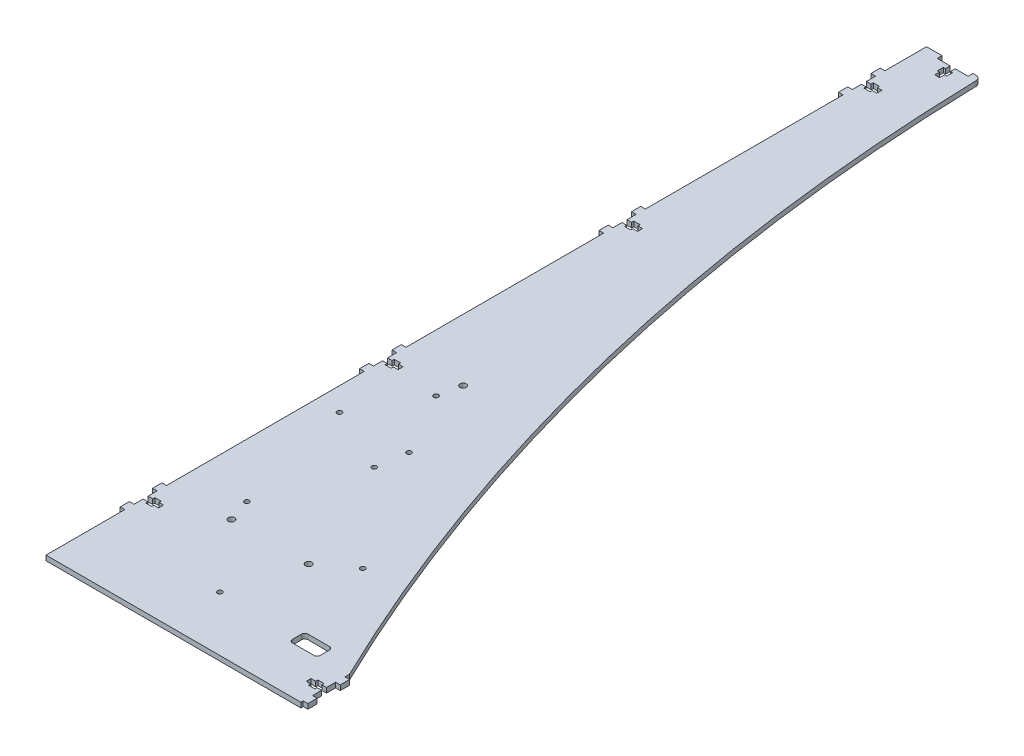
SolidWorks part; units mm, degrees
ref_plane "Alzado" through (0, 0, 0) normal (0, 0, 1) x (1, 0, 0)
ref_plane "Planta" through (0, 0, 0) normal (0, 1, 0) x (1, 0, 0)
ref_plane "Vista lateral" through (0, 0, 0) normal (1, 0, 0) x (0, 0, -1)
sketch "Croquis1" plane through (0, 0, 0) normal (0, 1, 0) x (1, 0, 0)
  line L0 (7, 66.1) -> (10, 66.1)
  line L1 (0, 0) -> (165, 0)
  line L2 (0, 0) -> (0, 51)
  line L3 (0, 570) -> (10, 570)
  line L4 (165, 0) -> (165, 1.5)
  line L5 (0, 51) -> (-3, 51)
  line L7 (0, 57) -> (-3, 57)
  line L8 (-3, 51) -> (-3, 57)
  line L9 (0, 72) -> (-3, 72)
  line L11 (0, 78) -> (-3, 78)
  line L12 (-3, 72) -> (-3, 78)
  line L13 (0, 66.1) -> (3, 66.1)
  line L15 (0, 62.9) -> (3, 62.9)
  line L16 (10, 66.1) -> (10, 62.9)
  line L17 (7, 67.5) -> (3, 67.5)
  line L18 (7, 67.5) -> (7, 66.1)
  line L19 (7, 61.5) -> (3, 61.5)
  line L20 (3, 67.5) -> (3, 66.1)
  line L21 (3, 62.9) -> (3, 61.5)
  line L22 (7, 62.9) -> (7, 61.5)
  line L23 (7, 62.9) -> (10, 62.9)
  line L24 (0, 66.1) -> (0, 72)
  line L25 (0, 78) -> (0, 206)
  line L26 (0, 57) -> (0, 62.9)
  line L27 (0, 233) -> (-3, 233)
  line L28 (-3, 227) -> (-3, 233)
  line L29 (0, 227) -> (-3, 227)
  line L30 (0, 221.1) -> (3, 221.1)
  line L31 (3, 222.5) -> (3, 221.1)
  line L32 (7, 222.5) -> (3, 222.5)
  line L33 (7, 222.5) -> (7, 221.1)
  line L34 (7, 221.1) -> (10, 221.1)
  line L35 (10, 221.1) -> (10, 217.9)
  line L36 (7, 217.9) -> (10, 217.9)
  line L37 (7, 217.9) -> (7, 216.5)
  line L38 (7, 216.5) -> (3, 216.5)
  line L39 (3, 217.9) -> (3, 216.5)
  line L40 (0, 217.9) -> (3, 217.9)
  line L41 (0, 212) -> (-3, 212)
  line L42 (-3, 206) -> (-3, 212)
  line L43 (0, 206) -> (-3, 206)
  line L44 (0, 388) -> (-3, 388)
  line L45 (-3, 382) -> (-3, 388)
  line L46 (0, 382) -> (-3, 382)
  line L47 (0, 376.1) -> (3, 376.1)
  line L48 (3, 377.5) -> (3, 376.1)
  line L49 (7, 377.5) -> (3, 377.5)
  line L50 (7, 377.5) -> (7, 376.1)
  line L51 (7, 376.1) -> (10, 376.1)
  line L52 (10, 376.1) -> (10, 372.9)
  line L53 (7, 372.9) -> (10, 372.9)
  line L54 (7, 372.9) -> (7, 371.5)
  line L55 (7, 371.5) -> (3, 371.5)
  line L56 (3, 372.9) -> (3, 371.5)
  line L57 (0, 372.9) -> (3, 372.9)
  line L58 (0, 367) -> (-3, 367)
  line L59 (-3, 361) -> (-3, 367)
  line L60 (0, 361) -> (-3, 361)
  line L61 (0, 388) -> (0, 516)
  line L62 (0, 376.1) -> (0, 382)
  line L63 (0, 367) -> (0, 372.9)
  line L64 (0, 233) -> (0, 361)
  line L65 (0, 221.1) -> (0, 227)
  line L66 (0, 212) -> (0, 217.9)
  line L67 (21.6, 566.9) -> (30, 566.9)
  line L69 (10, 570) -> (10, 566.9)
  line L70 (10, 566.9) -> (18.4, 566.9)
  line L71 (30, 570) -> (30, 566.9)
  line L73 (18.4, 566.9) -> (18.4, 563.9)
  line L74 (18.4, 556.9) -> (21.6, 556.9)
  line L75 (21.6, 566.9) -> (21.6, 563.9)
  line L76 (17, 563.9) -> (18.4, 563.9)
  line L77 (17, 563.9) -> (17, 559.9)
  line L78 (17, 559.9) -> (18.4, 559.9)
  line L79 (23, 563.9) -> (23, 559.9)
  line L80 (21.6, 563.9) -> (23, 563.9)
  line L81 (18.4, 559.9) -> (18.4, 556.9)
  line L82 (21.6, 559.9) -> (21.6, 556.9)
  line L83 (21.6, 559.9) -> (23, 559.9)
  line L84 (30, 570) -> (165, 570)
  line L85 (158, 13.4) -> (158, 12)
  line L86 (165, 1.5) -> (168, 1.5)
  line L88 (165, 7.5) -> (168, 7.5)
  line L89 (168, 1.5) -> (168, 7.5)
  line L90 (165, 22.5) -> (168, 22.5)
  line L92 (165, 28.5) -> (168, 28.5)
  line L93 (168, 22.5) -> (168, 28.5)
  line L94 (165, 16.6) -> (162, 16.6)
  line L96 (165, 13.4) -> (162, 13.4)
  line L97 (155, 16.6) -> (155, 13.4)
  line L98 (158, 18) -> (162, 18)
  line L99 (158, 18) -> (158, 16.6)
  line L100 (158, 12) -> (162, 12)
  line L101 (162, 18) -> (162, 16.6)
  line L102 (158, 16.6) -> (155, 16.6)
  line L103 (162, 13.4) -> (162, 12)
  line L104 (158, 13.4) -> (155, 13.4)
  line L105 (165, 16.6) -> (165, 22.5)
  line L106 (165, 7.5) -> (165, 13.4)
  line L107 (165, 28.5) -> (165, 570)
  line L108 (0, 543) -> (-3, 543)
  line L109 (-3, 537) -> (-3, 543)
  line L110 (0, 537) -> (-3, 537)
  line L111 (0, 531.1) -> (3, 531.1)
  line L112 (3, 532.5) -> (3, 531.1)
  line L113 (7, 532.5) -> (3, 532.5)
  line L114 (7, 532.5) -> (7, 531.1)
  line L115 (7, 531.1) -> (10, 531.1)
  line L116 (10, 531.1) -> (10, 527.9)
  line L117 (7, 527.9) -> (10, 527.9)
  line L118 (7, 527.9) -> (7, 526.5)
  line L119 (7, 526.5) -> (3, 526.5)
  line L120 (3, 527.9) -> (3, 526.5)
  line L121 (0, 527.9) -> (3, 527.9)
  line L122 (0, 522) -> (-3, 522)
  line L123 (-3, 516) -> (-3, 522)
  line L124 (0, 516) -> (-3, 516)
  line L125 (0, 543) -> (0, 570)
  line L126 (0, 522) -> (0, 527.9)
  line L127 (0, 531.1) -> (0, 537)
  dimension "D1" = 570
  dimension "D2" = 165
  dimension "D3" = 3
  dimension "D4" = 6
  dimension "D5" = 3
  dimension "D6" = 6
  dimension "D7" = 15
  dimension "D8" = 10
  dimension "D9" = 3.2
  dimension "D10" = 5.9
  dimension "D11" = 4
  dimension "D12" = 6
  dimension "D13" = 1.4
  dimension "D14" = 51
  dimension "D15" = 3
  dimension "D17" = 155
  dimension "D18" = 20
  dimension "D19" = 10
  dimension "D20" = 3.1
  dimension "D21" = 10
  dimension "D22" = 3.2
  dimension "D23" = 4
  dimension "D24" = 6
  dimension "D25" = 1.4
  dimension "D26" = 8.4
  dimension "D27" = 3
  dimension "D28" = 6
  dimension "D29" = 6
  dimension "D30" = 3
  dimension "D31" = 3
  dimension "D32" = 3.2
  dimension "D33" = 4
  dimension "D34" = 6
  dimension "D35" = 1.4
  dimension "D36" = 10
  dimension "D37" = 3
  dimension "D38" = 15
  dimension "D39" = 5.9
  dimension "D40" = 1.5
  dimension "D16" = 4
extrude "Saliente-Extruir1" add sketch "Croquis1" along normal blind 3.2
sketch "Croquis3" plane through (0, 3.2, 0) normal (0, 1, 0) x (1, 0, 0)
  line L0 (0, 217.9) -> (0, 212) construction
  line L1 (0, 0) -> (165, 0) construction
  circle A0 centre (40, 80) radius 2.05
  circle A1 centre (90, 80) radius 2.05
  circle A2 centre (40, 230) radius 2.05
  dimension "D1" = 4.1
  dimension "D2" = 50
  dimension "D3" = 150
  dimension "D4" = 40
  dimension "D5" = 80
extrude "Cortar-Extruir2" cut sketch "Croquis3" against normal up to surface (3.2 mm away) up to face at (34.1167, 0, -285.1383)
sketch "Croquis4" plane through (0, 0, 0) normal (0, -1, 0) x (1, 0, 0)
  line L1 (0, 0) -> (165, 0) construction
  line L4 (143, -30.5) -> (129, -30.5)
  line L5 (145, -32.5) -> (145, -38.5)
  line L6 (143, -40.5) -> (129, -40.5)
  line L7 (127, -32.5) -> (127, -38.5)
  line L8 (165, -28.5) -> (165, -570) construction
  arc A14 (143, -30.5) -> (145, -32.5) centre (143, -32.5) cw
  arc A15 (127, -38.5) -> (129, -40.5) centre (129, -38.5) ccw
  arc A16 (127, -32.5) -> (129, -30.5) centre (129, -32.5) cw
  arc A17 (145, -38.5) -> (143, -40.5) centre (143, -38.5) cw
  point P38 (145, -30.5)
  point P41 (127, -40.5)
  point P46 (145, -40.5)
  dimension "D3" = 20
  dimension "D20" = 2
  dimension "D16" = 18
  dimension "D17" = 10
  dimension "D19" = 30.5
extrude "Cortar-Extruir3" cut sketch "Croquis4" against normal up to surface (3.2 mm away) up to face at (40, 3.2, -227.95)
sketch "Croquis5" plane through (0, 0, 0) normal (0, -1, 0) x (1, 0, 0)
  line L0 (165, -570) -> (30, -570) construction
  line L1 (165, -28.5) -> (165, -570) construction
  line L2 (35, -570) -> (165, -570)
  line L3 (165, -570) -> (165, -31.5)
  arc A0 (35, -570) -> (165, -31.5) centre (1334.6806, -598.8159) cw
  dimension "D3" = 1300
  dimension "D1" = 5
  dimension "D2" = 3
extrude "Cortar-Extruir4" cut sketch "Croquis5" against normal up to surface (3.2 mm away) up to face at (136, 3.2, -35.5)
fillet "Redondeo1" radius 3 1 edges at (35, 1.6, -570)
sketch "Croquis6" plane through (0, 0, 0) normal (0, -1, 0) x (1, 0, 0)
  line L0 (0, -51) -> (0, 0) construction
  line L1 (0, 0) -> (165, 0) construction
  line L2 (0, -206) -> (0, -78) construction
  line L3 (127, -35.5) -> (77, -35.5) construction
  line L4 (127, -32.5) -> (127, -38.5) construction
  circle A0 centre (110, -95) radius 1.55
  circle A1 centre (35, -95) radius 1.55
  circle A2 centre (60, -175) radius 1.55
  circle A4 centre (15, -175) radius 1.55
  circle A5 centre (77, -35.5) radius 1.55
  circle A6 centre (37, -215.5) radius 1.55
  circle A7 centre (57, -155.5) radius 1.55
  dimension "D1" = 3.1
  dimension "D2" = 75
  dimension "D3" = 35
  dimension "D4" = 95
  dimension "D5" = 45
  dimension "D6" = 15
  dimension "D7" = 80
  dimension "D8" = 50
  dimension "D9" = 180
  dimension "D10" = 40
  dimension "D11" = 120
  dimension "D12" = 20
extrude "Cortar-Extruir5" cut sketch "Croquis6" against normal up to surface (3.2 mm away) up to face at (33.8773, 3.2, -285.3182)
